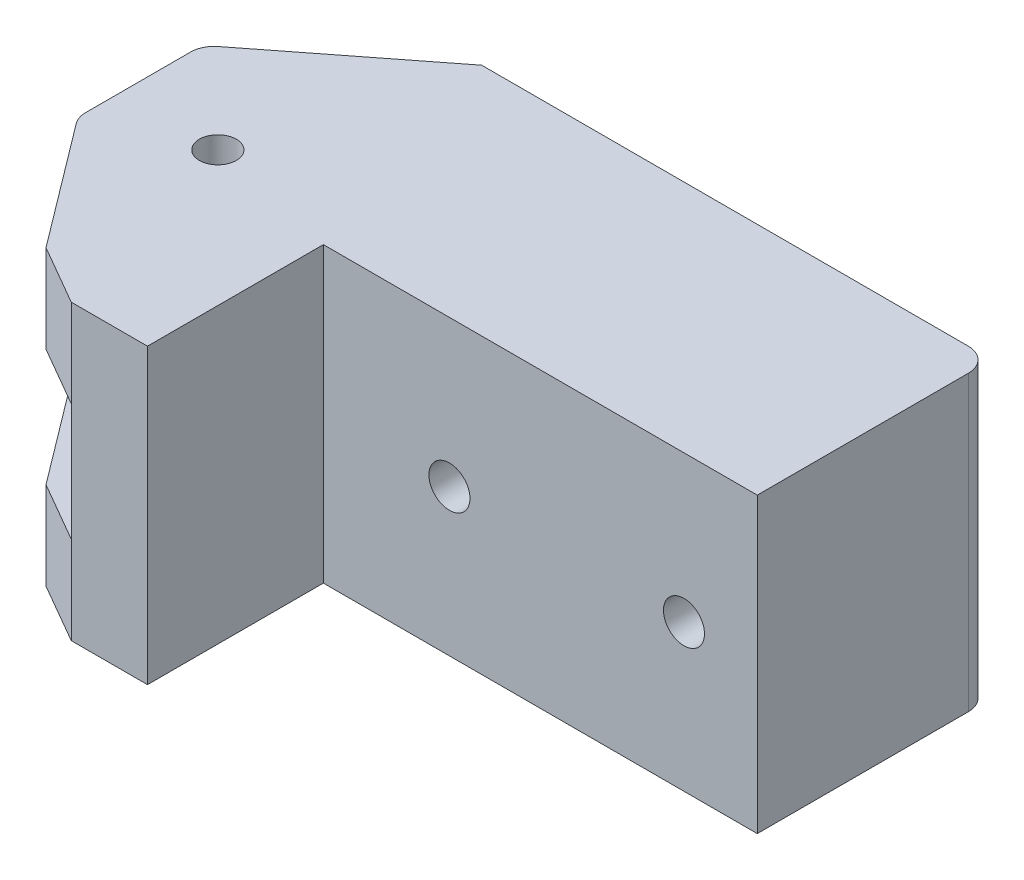
SolidWorks part; units mm, degrees
ref_plane "Front Plane" through (0, 0, 0) normal (0, 0, 1) x (1, 0, 0)
ref_plane "Top Plane" through (0, 0, 0) normal (0, 1, 0) x (1, 0, 0)
ref_plane "Right Plane" through (0, 0, 0) normal (1, 0, 0) x (0, 0, -1)
sketch "Sketch1" plane through (0, 0, 0) normal (0, 1, 0) x (1, 0, 0)
  line L0 (0, 0) -> (-43.5, 0)
  line L1 (-43.5, 0) -> (-43.5, -35) construction
  line L2 (-43.5, -35) -> (-37, -35)
  line L3 (-37, -35) -> (-37, -20)
  line L4 (-37, -20) -> (0, -20)
  line L5 (0, -20) -> (0, 0)
  line L6 (-43.5, 0) -> (-56.8853, -10.4577)
  line L7 (-56.8853, -10.4577) -> (-56.8853, -21.0577)
  line L8 (-56.8853, -21.0577) -> (-48.5962, -32.0577)
  line L9 (-48.5962, -32.0577) -> (-43.5, -35)
  line L10 (-43.5, -17.5) -> (-48.5, -17.5) construction
  circle A0 centre (-48.5, -17.5) radius 1.575
  dimension "D11" = 3.15
  dimension "D1" = 43.5
  dimension "D2" = 35
  dimension "D3" = 20
  dimension "D4" = 37
  dimension "D5" = 30
  dimension "D6" = 38
  dimension "D7" = 10.6
  dimension "D8" = 37
  dimension "D9" = 11
  dimension "D10" = 5
extrude "Boss-Extrude1" add sketch "Sketch1" along normal mid plane 25
sketch "Sketch2" plane through (0, 0, 35) normal (0, 0, 1) x (1, 0, 0)
  line L0 (-43.5, 12.5) -> (-43.5, -12.5) construction
  line L1 (-43.5, -5) -> (-56.8853, -5)
  line L2 (-43.5, -5) -> (-43.5, 5)
  line L3 (-43.5, 5) -> (-56.8853, 5)
  line L4 (-56.8853, -5) -> (-56.8853, 5)
  line L5 (-56.8853, 12.5) -> (-56.8853, -12.5) construction
  line L6 (-56.8853, 12.5) -> (-48.5962, 12.5) construction
  dimension "D1" = 7.5
  dimension "D2" = 10
extrude "Cut-Extrude1" cut sketch "Sketch2" against normal through all
sketch "Sketch3" plane through (0, 0, 20) normal (0, 0, 1) x (1, 0, 0)
  line L0 (0, 12.5) -> (0, -12.5) construction
  line L1 (0, 0) -> (-26.25, 0) construction
  circle A0 centre (-26.25, 0) radius 1.75
  circle A1 centre (-6.25, 0) radius 1.75
  dimension "D1" = 3.5
  dimension "D2" = 26.25
  dimension "D3" = 6.25
extrude "Cut-Extrude2" cut sketch "Sketch3" against normal blind 25
sketch "Sketch4" plane through (0, 0, 0) normal (0, 0, -1) x (-1, 0, 0)
  circle A0 centre (6.25, 0) radius 4
  circle A2 centre (26.25, 0) radius 4
extrude "Cut-Extrude3" cut sketch "Sketch4" against normal blind 4
fillet "Fillet1" radius 2 5 edges at (0, 0, 0) (-56.8853, 8.75, 10.4577) (-56.8853, 8.75, 21.0577) (-56.8853, -8.75, 21.0577) (-56.8853, -8.75, 10.4577)
